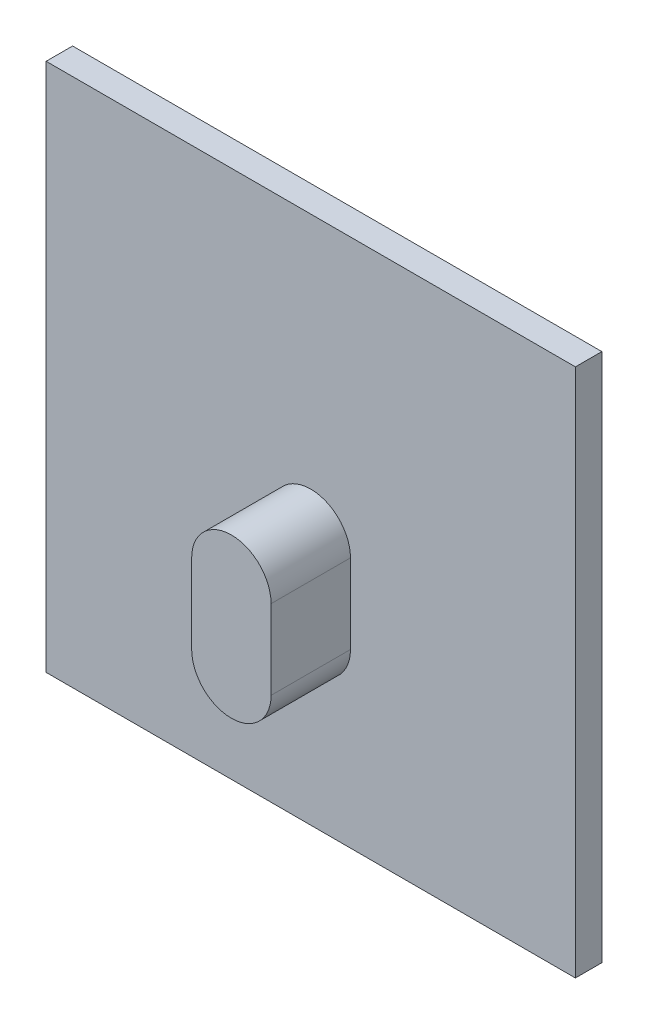
SolidWorks part; units mm, degrees
ref_plane "정면" through (0, 0, 0) normal (0, 0, 1) x (1, 0, 0)
ref_plane "윗면" through (0, 0, 0) normal (0, 1, 0) x (1, 0, 0)
ref_plane "우측면" through (0, 0, 0) normal (1, 0, 0) x (0, 0, -1)
sketch "스케치1" plane through (0, 0, 0) normal (0, 0, 1) x (1, 0, 0)
  line L0 (0, 0) -> (419.8582, 0) construction
  line L1 (0, 0) -> (0, 275.8865) construction
  line L2 (0, -10) -> (-39.773, -10) construction
  line L3 (-20, -20) -> (20, -20)
  line L4 (-20, -20) -> (-20, 20)
  line L5 (-20, 20) -> (20, 20)
  line L6 (20, -20) -> (20, 20)
  line L7 (-20, -20) -> (20, 20) construction
  line L8 (-20, 20) -> (20, -20) construction
  line L9 (0, 2) -> (-34.5471, 2) construction
  line L10 (-3, -7) -> (-3, -1)
  line L11 (3, -1) -> (3, -7)
  circle A1 centre (0, -7) radius 3
  circle A2 centre (0, -1) radius 3
  dimension "D3" = 6
  dimension "D4" = 13
  dimension "D5" = 6
  dimension "D6" = 6
  dimension "D1" = 40
  dimension "D2" = 40
extrude "보스-돌출1" add sketch "스케치1" along normal blind 2 contours L3 L6 L5 L4 A2 L11 A1 L10 region at (-19.4343, 0, 0)
extrude "보스-돌출2" add sketch "스케치1<3>" along normal blind 8 contours A2 | A2 L10 A1 | A2 A1 L11 | A1 region at (0, -7, 0) region at (-2.3299, -4, 0) region at (0, -1, 0) region at (2.3299, -4, 0)
sketch "스케치1<3>" plane through (0, 0, 0) normal (0, 0, 1) x (1, 0, 0) same geometry as "스케치1"
